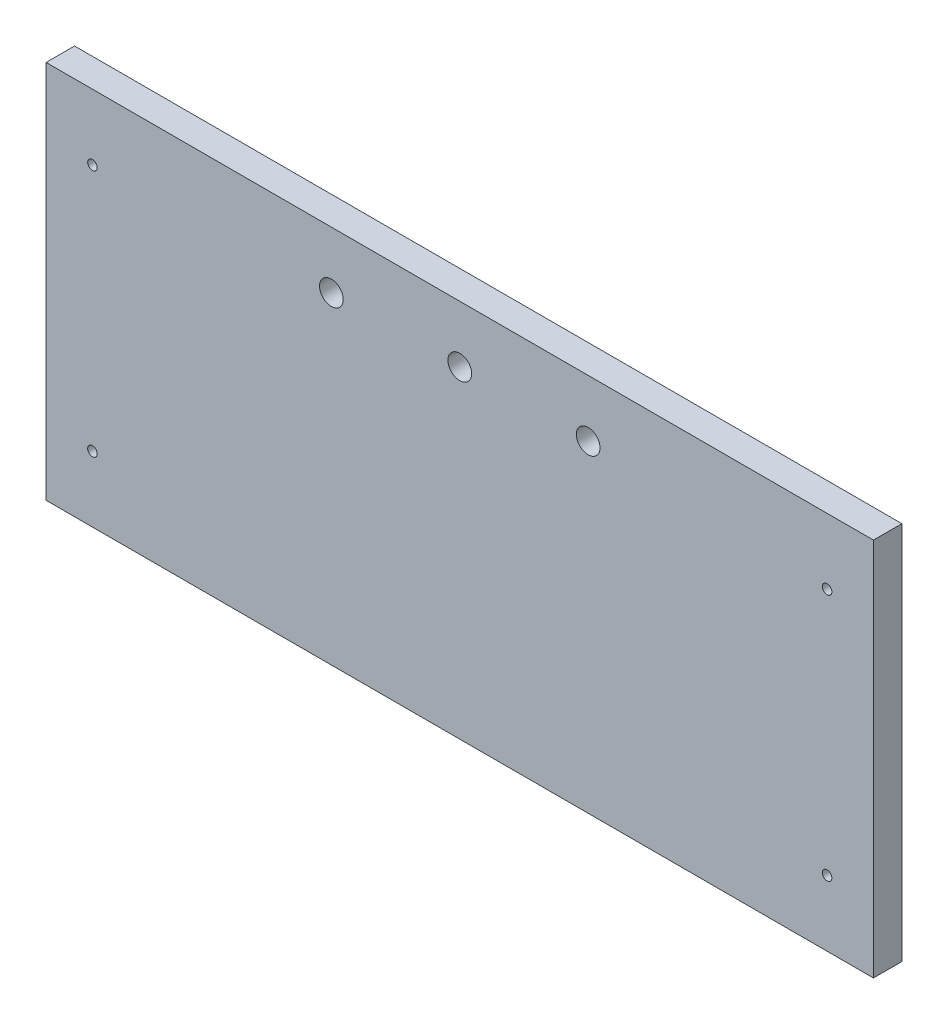
SolidWorks part; units mm, degrees
ref_plane "Front Plane" through (0, 0, 0) normal (0, 0, 1) x (1, 0, 0)
ref_plane "Top Plane" through (0, 0, 0) normal (0, 1, 0) x (1, 0, 0)
ref_plane "Right Plane" through (0, 0, 0) normal (1, 0, 0) x (0, 0, -1)
sketch "Sketch1" plane through (0, 0, 0) normal (0, 0, 1) x (1, 0, 0)
  line L1 (0, 0) -> (277.05, 0)
  line L2 (0, 0) -> (0, 127)
  line L3 (0, 127) -> (277.05, 127)
  line L4 (277.05, 0) -> (277.05, 127)
  line L5 (9.525, 127) -> (9.525, 0) construction
  line L7 (267.525, 127) -> (267.525, 0) construction
  circle A3 centre (15.525, 105) radius 1.6
  circle A4 centre (15.525, 22) radius 1.6
  circle A5 centre (261.525, 105) radius 1.6
  circle A6 centre (261.525, 22) radius 1.6
  dimension "D14" = 3.2
  dimension "D17" = 3.2
  dimension "D19" = 3.2
  dimension "D20" = 3.2
  dimension "D1" = 127
  dimension "D2" = 277.05
  dimension "D3" = 9.525
  dimension "D5" = 9.525
  dimension "D13" = 6
  dimension "D15" = 22
  dimension "D16" = 6
  dimension "D18" = 22
  dimension "D21" = 6
  dimension "D22" = 6
  dimension "D23" = 22
  dimension "D24" = 22
extrude "Wall" add sketch "Sketch1" along normal blind 9.525
sketch "Sketch2" plane through (0, 0, 9.525) normal (0, 0, 1) x (1, 0, 0)
  line L0 (277.05, 127) -> (0, 127) construction
  line L1 (0, 127) -> (0, 0) construction
  line L2 (95.53, 107.95) -> (138.525, 107.95) construction
  line L3 (181.52, 107.95) -> (138.525, 107.95) construction
  circle A0 centre (138.525, 107.95) radius 3.97
  circle A1 centre (95.53, 107.95) radius 3.97
  circle A2 centre (181.52, 107.95) radius 3.97
  point P4 (138.525, 127)
  dimension "D2" = 19.05
  dimension "D3" = 95.53
extrude "RodCutouts" cut sketch "Sketch2" against normal up to next
sketch "Sketch3" [suppressed] plane through (0, 0, 9.525) normal (0, 0, 1) x (1, 0, 0)
  line L0 (277.05, 127) -> (0, 127) construction
  line L1 (50.8, 88.9) -> (226.25, 88.9)
  line L2 (50.8, 88.9) -> (50.8, 114.3)
  line L3 (50.8, 114.3) -> (226.25, 114.3)
  line L4 (226.25, 88.9) -> (226.25, 114.3)
  line L5 (50.8, 88.9) -> (226.25, 114.3) construction
  line L6 (50.8, 114.3) -> (226.25, 88.9) construction
  line L7 (0, 127) -> (0, 0) construction
  point P0 (138.525, 101.6)
  point P9 (138.525, 127)
  dimension "D1" = 25.4
  dimension "D2" = 50.8
  dimension "D3" = 25.4
extrude "CannulusLargeCutout" [suppressed] cut sketch "Sketch3" against normal up to next
sketch "Sketch4" [suppressed] plane through (0, 0, 9.525) normal (0, 0, 1) x (1, 0, 0)
  line L0 (15.525, 103.5) -> (261.525, 103.5) construction
  line L1 (15.525, 105) -> (15.525, 22) construction
  line L2 (261.525, 105) -> (261.525, 22) construction
  circle A0 centre (38.525, 103.5) radius 9
  circle A1 centre (38.525, 63.5) radius 9
  circle A2 centre (88.525, 63.5) radius 9
  circle A3 centre (138.525, 63.5) radius 9
  circle A4 centre (88.525, 103.5) radius 9
  circle A5 centre (138.525, 103.5) radius 9
  circle A6 centre (188.525, 103.5) radius 9
  circle A7 centre (238.525, 103.5) radius 9
  circle A8 centre (188.525, 63.5) radius 9
  circle A9 centre (238.525, 63.5) radius 9
  circle A10 centre (38.525, 23.5) radius 9
  circle A11 centre (88.525, 23.5) radius 9
  circle A12 centre (138.525, 23.5) radius 9
  circle A13 centre (188.525, 23.5) radius 9
  circle A14 centre (238.525, 23.5) radius 9
  point P9 (15.525, 63.5)
  point P23 (138.525, 103.5)
  dimension "D1" = 18
  dimension "D2" = 5
  dimension "D4" = 3
extrude "CannulusHoles" [suppressed] cut sketch "Sketch4" against normal up to next
equation "\"Length\"= 283mm"
equation "\"Width\"= 225mm"
equation "\"WallThickness\"= 12.5mm"
equation "\"UpperWaterJacketThickness\"= 28mm"
equation "\"SpacerHeight\"= 80.2mm"
equation "\"SpacerCornerWidth\"= 10mm"
equation "\"SpacerCornerHeight\"= 60.16mm"
equation "\"SpacerPegDiameter\"= 10mm"
equation "\"SpacerPegHeight\"= 10mm"
equation "\"TubingShort\"= 110mm"
equation "\"TubingLong\"= 175mm"
equation "\"PlateLength\"= 252mm"
equation "\"PlateWidth\"= 190mm"
equation "\"PlateHoleDiameter\"= 5.9mm"
equation "\"PlateHoleBottom\"= 2mm"
equation "\"PlateHoleSide\"= 1.55mm"
equation "\"PlateHoleSpacing\"= 3.1mm"
equation "\"PlateThickness\"= 1.55mm"
equation "\"ReservoirBottom\"= 12.5mm"
equation "\"ReservoirSupportWidth\"= 12mm"
equation "\"ReservoirSupportHeight\"= 15.1mm"
equation "\"ReservoirSupportPlacementHeight\"= 50mm"
equation "\"ReservoirHoleDiameter\"= 12.7mm"
equation "\"ReservoirHoleRight\"= 25mm"
equation "\"ReservoirHoleTop\"= \"ReservoirSupportPlacementHeight\""
equation "\"ReservoirHeight\"= 90mm"
equation "\"ReservoirPortBottom\"= 4mm"
equation "\"ReservoirPortTop\"= 10mm"
equation "\"ReservoirPortWidth\"= 101mm"
equation "\"CustomSpacerWallThickness\"= 0.375in"
equation "\"CustomSpacerHeight\"= 5in"
equation "\"CustomSpacerRodHoleHeight\"= .75in"
equation "\"CustomSpacerRodHoleDiameter\"= .3125in"
equation "\"ScrewBlockSide\"= 12mm"
equation "\"ScrewBlockUpperHeight\"= 16mm"
equation "\"ScrewBlockLowerHeight\"= 16mm"
equation "\"InternalLength\"= \"Length\" - ( 2 * \"WallThickness\" )"
equation "\"InternalWidth\"= \"Width\" - ( 2 * \"WallThickness\" )"
equation "\"CustomSpacerPegHeight\"= 1in"
equation "\"CustomSpacerScrewBore\"=3.2mm"
equation "\"CustomSpacerScrewDepth\"=10mm"
equation "\"D1@Sketch1\"=\"CustomSpacerHeight\""
equation "\"D2@Sketch1\"=\"InternalLength\"+\"CustomSpacerWallThickness\"*2"
equation "\"D3@Sketch1\"=\"CustomSpacerWallThickness\""
equation "\"D5@Sketch1\"=\"CustomSpacerWallThickness\""
equation "\"D1@Wall\" = \"CustomSpacerWallThickness\""
equation "\"D13@Sketch1\"=\"ScrewBlockSide\"/2"
equation "\"D14@Sketch1\"=\"CustomSpacerScrewBore\""
equation "\"D15@Sketch1\"=\"ScrewBlockUpperHeight\"+\"ScrewBlockSide\"/2"
equation "\"D16@Sketch1\"=\"ScrewBlockSide\"/2"
equation "\"D17@Sketch1\"=\"CustomSpacerScrewBore\""
equation "\"D18@Sketch1\"=\"ScrewBlockLowerHeight\"+\"ScrewBlockSide\"/2"
equation "\"D19@Sketch1\"=\"CustomSpacerScrewBore\""
equation "\"D20@Sketch1\"=\"CustomSpacerScrewBore\""
equation "\"D21@Sketch1\"=\"ScrewBlockSide\"/2"
equation "\"D22@Sketch1\"=\"ScrewBlockSide\"/2"
equation "\"D23@Sketch1\"=\"ScrewBlockLowerHeight\"+\"ScrewBlockSide\"/2"
equation "\"D24@Sketch1\"=\"ScrewBlockUpperHeight\"+\"ScrewBlockSide\"/2"
equation "\"RodCutout\"=7.94"
equation "\"D1@Sketch2\"=\"RodCutout\""
equation "\"D3@Sketch2\"=86mm+9.53mm"
equation "\"CannulusTubingDiameter\"=15"
equation "\"D1@Sketch4\"=\"CannulusTubingDiameter\" * 1.2"
